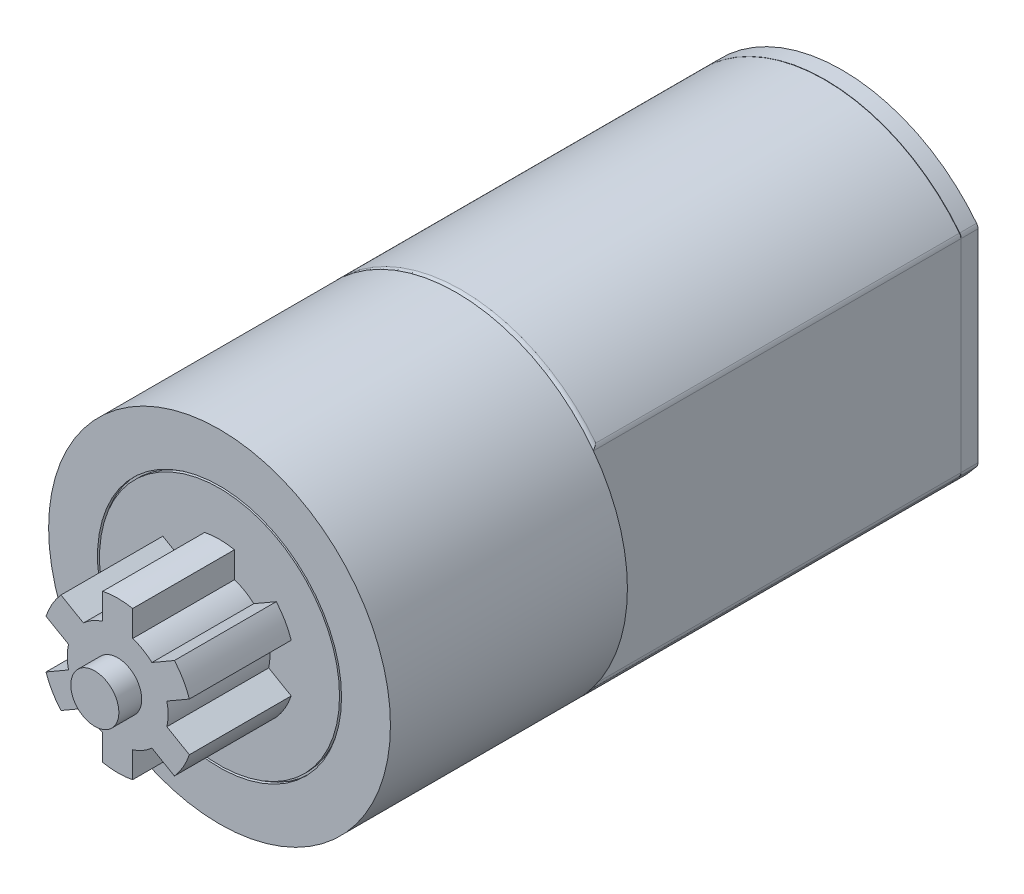
SolidWorks part; units mm, degrees
ref_plane "Front Plane" through (0, 0, 0) normal (0, 0, 1) x (1, 0, 0)
ref_plane "Top Plane" through (0, 0, 0) normal (0, 1, 0) x (1, 0, 0)
ref_plane "Right Plane" through (0, 0, 0) normal (1, 0, 0) x (0, 0, -1)
sketch "Sketch1" plane through (0, 0, 0) normal (0, 0, 1) x (1, 0, 0)
  circle A0 centre (0, 0) radius 5.085
  dimension "D1" = 10.17
extrude "Boss-Extrude1" add sketch "Sketch1" along normal blind 23.23
sketch "Sketch2" plane through (0, 0, 0) normal (0, 0, -1) x (-1, 0, 0)
  circle A0 centre (0, 0) radius 5.085
  circle A1 centre (0, 0) radius 2
  dimension "D1" = 4
extrude "Cut-Extrude1" cut sketch "Sketch2" against normal blind 1 contours A0 | A1
sketch "Sketch4" plane through (0, 0, 0) normal (0, 0, -1) x (-1, 0, 0)
  circle A0 centre (0, 0) radius 0.8
  dimension "D1" = 1.6
extrude "Cut-Extrude2" cut sketch "Sketch4" against normal blind 0.5
sketch "Sketch5" plane through (0, 0, 0) normal (0, 0, -1) x (-1, 0, 0)
  line L0 (-10.1891, 0) -> (11.0581, 0) construction
  line L2 (-7.5369, -5.085) -> (-4.045, -5.085)
  line L3 (-7.5369, -5.085) -> (-7.5369, 5.085)
  line L4 (-7.5369, 5.085) -> (-4.045, 5.085)
  line L5 (-4.045, -5.085) -> (-4.045, 5.085)
  line L6 (-7.5369, -5.085) -> (-4.045, 5.085) construction
  line L7 (-7.5369, 5.085) -> (-4.045, -5.085) construction
  line L8 (8.0438, -5.085) -> (4.045, -5.085)
  line L9 (8.0438, -5.085) -> (8.0438, 5.085)
  line L10 (8.0438, 5.085) -> (4.045, 5.085)
  line L11 (4.045, -5.085) -> (4.045, 5.085)
  line L12 (8.0438, -5.085) -> (4.045, 5.085) construction
  line L13 (8.0438, 5.085) -> (4.045, -5.085) construction
  point P3 (-5.791, 0)
  point P8 (6.0444, 0)
  dimension "D1" = 8.09
  dimension "D2" = 4.045
extrude "Cut-Extrude3" cut sketch "Sketch5" against normal blind 12.47 contours L11 L8 L9 L10 | L11 | L4 L5 L2 L3 region at (-6.0444, 0, 0)
sketch "Sketch6" plane through (0, 0, 23.23) normal (0, 0, 1) x (1, 0, 0)
  circle A0 centre (0, 0) radius 2.25
  circle A1 centre (0, 0) radius 5.085
  dimension "D1" = 4.5
extrude "Cut-Extrude4" cut sketch "Sketch6" against normal blind 3.71 contours A0 | A1
sketch "Sketch7" plane through (0, 0, 19.52) normal (0, 0, 1) x (1, 0, 0)
  circle A0 centre (0, 0) radius 3.57
  circle A1 centre (0, 0) radius 3.63
  dimension "D1" = 7.14
  dimension "D2" = 7.26
extrude "Cut-Extrude5" cut sketch "Sketch7" against normal blind 0.1
sketch "Sketch8" plane through (0, 0, 23.23) normal (0, 0, 1) x (1, 0, 0)
  circle A0 centre (0, 0) radius 2.25
  circle A1 centre (0, 0) radius 0.715
  circle M1 centre (0, 0) radius 2.25
  dimension "D1" = 1.43
extrude "Cut-Extrude6" cut sketch "Sketch8" against normal blind 0.68 contours A1 M1 region at (-2.1864, 0, 23.23)
sketch "Sketch9" plane through (0, 0, 22.55) normal (0, 0, 1) x (1, 0, 0)
  line L0 (0, 0) -> (0, 2.25) construction
  line L1 (-0.445, 0.5) -> (0.445, 0.5)
  line L2 (-0.445, 0.5) -> (-0.445, 2.5)
  line L3 (-0.445, 2.5) -> (0.445, 2.5)
  line L4 (0.445, 0.5) -> (0.445, 2.5)
  line L5 (-0.445, 0.5) -> (0.445, 2.5) construction
  line L6 (-0.445, 2.5) -> (0.445, 0.5) construction
  line L7 (0.2105, 0.6354) -> (1.9426, 1.6354)
  line L8 (1.9426, 1.6354) -> (2.3876, 0.8646)
  line L9 (0.6555, -0.1354) -> (2.3876, 0.8646)
  line L10 (0.2105, 0.6354) -> (0.6555, -0.1354)
  line L11 (0.2105, 0.6354) -> (2.3876, 0.8646) construction
  line L12 (1.9426, 1.6354) -> (0.6555, -0.1354) construction
  line L13 (0.6555, 0.1354) -> (2.3876, -0.8646)
  line L14 (2.3876, -0.8646) -> (1.9426, -1.6354)
  line L15 (0.2105, -0.6354) -> (1.9426, -1.6354)
  line L16 (0.6555, 0.1354) -> (0.2105, -0.6354)
  line L17 (0.6555, 0.1354) -> (1.9426, -1.6354) construction
  line L18 (2.3876, -0.8646) -> (0.2105, -0.6354) construction
  line L19 (0.445, -0.5) -> (0.445, -2.5)
  line L20 (0.445, -2.5) -> (-0.445, -2.5)
  line L21 (-0.445, -0.5) -> (-0.445, -2.5)
  line L22 (0.445, -0.5) -> (-0.445, -0.5)
  line L23 (0.445, -0.5) -> (-0.445, -2.5) construction
  line L24 (0.445, -2.5) -> (-0.445, -0.5) construction
  line L25 (-0.2105, -0.6354) -> (-1.9426, -1.6354)
  line L26 (-1.9426, -1.6354) -> (-2.3876, -0.8646)
  line L27 (-0.6555, 0.1354) -> (-2.3876, -0.8646)
  line L28 (-0.2105, -0.6354) -> (-0.6555, 0.1354)
  line L29 (-0.2105, -0.6354) -> (-2.3876, -0.8646) construction
  line L30 (-1.9426, -1.6354) -> (-0.6555, 0.1354) construction
  line L31 (-0.6555, -0.1354) -> (-2.3876, 0.8646)
  line L32 (-2.3876, 0.8646) -> (-1.9426, 1.6354)
  line L33 (-0.2105, 0.6354) -> (-1.9426, 1.6354)
  line L34 (-0.6555, -0.1354) -> (-0.2105, 0.6354)
  line L35 (-0.6555, -0.1354) -> (-1.9426, 1.6354) construction
  line L36 (-2.3876, 0.8646) -> (-0.2105, 0.6354) construction
  circle A0 centre (0, 0) radius 1.5
  circle A1 centre (0, 0) radius 2.25
  point P3 (0, 1.5)
  point P33 (0, 0)
  circle M2 centre (0, 0) radius 2.25
  dimension "D1" = 3
  dimension "D4" = 6
  dimension "D2" = 0.89
  dimension "D3" = 2
extrude "Cut-Extrude7" cut sketch "Sketch9" against normal up to surface (3.03 mm away) contours A0 L2 L33 M2 | A0 L7 L4 M2 | A0 L13 L9 M2 | A0 L19 L15 M2 | A0 L25 L21 M2 | A0 L31 L27 M2 region at (-0.9473, 1.6407, 22.55) region at (0.9473, 1.6407, 22.55) region at (-1.8945, 0, 22.55) region at (1.8945, 0, 22.55) region at (-0.9473, -1.6407, 22.55) region at (0.9473, -1.6407, 22.55) up to face at (2.25, 0, 19.52)
sketch "Sketch10" plane through (0, 0, 1) normal (0, 0, -1) x (-1, 0, 0)
  line L0 (4.045, -3.0814) -> (4.045, 3.0814) construction
  circle A0 centre (2.5, -3.1452) radius 0.455
  dimension "D1" = 0.91
  dimension "D2" = 1.545
extrude "Boss-Extrude2" add sketch "Sketch10" along normal blind 0.68
sketch "Sketch11" plane through (0, 0, 12.47) normal (0, 0, -1) x (-1, 0, 0)
  circle A0 centre (0, 0) radius 5.085
  circle A1 centre (0, 0) radius 5.035
  dimension "D1" = 10.07
extrude "Cut-Extrude8" cut sketch "Sketch11" along normal blind 0.01 contours A1 | A0
fillet "Fillet3" radius 0.2 6 edges at (0, 5.085, 12.46) (-4.045, 3.0814, 6.73) (-4.045, -3.0814, 6.73) (4.045, 3.0814, 6.73) (4.045, -3.0814, 6.73) (0, -5.085, 12.46)
ref_plane "Plane1" through (0, 0, 1.5) normal (0, 0, -1) x (-1, 0, 0)
sketch "Sketch15" plane through (0, 0, 1.5) normal (0, 0, -1) x (-1, 0, 0)
  line L0 (-3.945, 3.1206) -> (-3.945, -3.1206)
  line L1 (3.945, 3.1206) -> (3.945, -3.1206)
  line L2 (4.045, -3.0132) -> (4.045, 3.0132)
  line L3 (-4.045, 3.0132) -> (-4.045, -3.0132)
  line L4 (4.045, -3.0132) -> (4.045, 3.0132)
  line L5 (-4.045, 3.0132) -> (-4.045, -3.0132)
  arc A0 (-3.945, -3.1206) -> (3.945, -3.1206) centre (0, 0) ccw
  arc A1 (3.945, 3.1206) -> (-3.9453, 3.1201) centre (0, 0) ccw
  arc A6 (4.045, 3.0132) -> (4.0024, 3.1365) centre (3.845, 3.0132) ccw
  arc A7 (4.0024, 3.1365) -> (-4.0024, 3.1365) centre (0, 0) ccw
  arc A8 (-4.0024, 3.1365) -> (-4.045, 3.0132) centre (-3.845, 3.0132) ccw
  arc A9 (-4.045, -3.0132) -> (-4.0024, -3.1365) centre (-3.845, -3.0132) ccw
  arc A10 (-4.0024, -3.1365) -> (4.0024, -3.1365) centre (0, 0) ccw
  arc A11 (4.0024, -3.1365) -> (4.045, -3.0132) centre (3.845, -3.0132) ccw
  arc A12 (4.045, 3.0132) -> (4.0024, 3.1365) centre (3.845, 3.0132) ccw
  arc A13 (4.0024, 3.1365) -> (-4.0024, 3.1365) centre (0, 0) ccw
  arc A14 (-4.0024, 3.1365) -> (-4.045, 3.0132) centre (-3.845, 3.0132) ccw
  arc A15 (-4.045, -3.0132) -> (-4.0024, -3.1365) centre (-3.845, -3.0132) ccw
  arc A16 (-4.0024, -3.1365) -> (4.0024, -3.1365) centre (0, 0) ccw
  arc A17 (4.0024, -3.1365) -> (4.045, -3.0132) centre (3.845, -3.0132) ccw
  dimension "D1" = 0
  dimension "D2" = 10.06
  dimension "D3" = 0.1
  dimension "D4" = 0.1
extrude "Cut-Extrude9" cut sketch "Sketch15" against normal blind 0.01 contours A16 A17 L4 A12 A13 A14 L5 A15 A1 L1 A0 L0 region at (-4.0218, -3.0742, 1.5)
